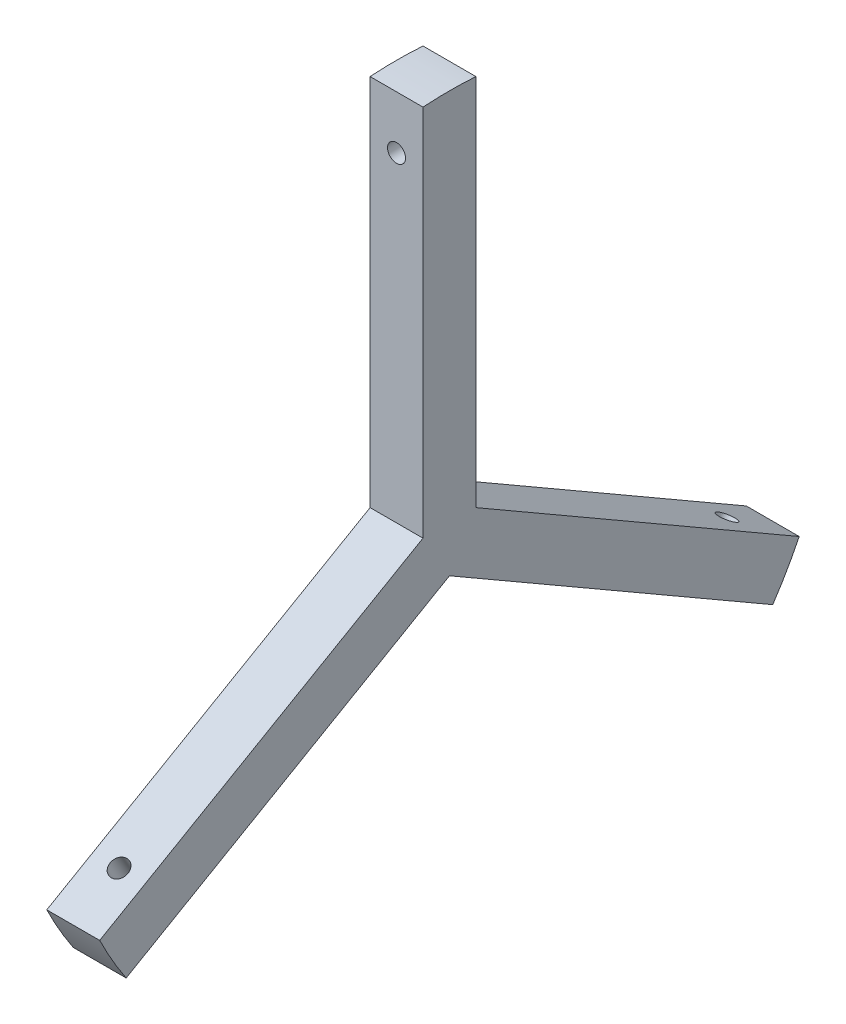
SolidWorks part; units mm, degrees
ref_plane "Plan de face" through (0, 0, 0) normal (0, 0, 1) x (1, 0, 0)
ref_plane "Plan de dessus" through (0, 0, 0) normal (0, 1, 0) x (1, 0, 0)
ref_plane "Plan de droite" through (0, 0, 0) normal (1, 0, 0) x (0, 0, -1)
sketch "Esquisse2" plane through (0, 0, 0) normal (0, 0, 1) x (1, 0, 0)
  line L0 (-5, 0) -> (5, 0)
  line L1 (5, 0) -> (5, 73.61)
  line L2 (5, 73.61) -> (-5, 73.61)
  line L3 (-5, 73.61) -> (-5, 0)
  dimension "D1" = 73.61
  dimension "D2" = 10
extrude "Boss.-Extru.1" add sketch "Esquisse2" along normal blind 5 and the other way blind 5
sketch "Esquisse3" plane through (5, 0, 0) normal (1, 0, 0) x (0, 0, -1)
  line L0 (0, 0) -> (0, 73.61) construction
  line L1 (-25.3992, 69.0892) -> (-25.3992, 83.5877)
  line L2 (-25.3992, 83.5877) -> (25.3992, 83.5877)
  line L3 (25.3992, 83.5877) -> (25.3992, 69.0892)
  line L4 (5, 75) -> (-5, 75) construction
  line L5 (-5, 0) -> (-5, 73.61) construction
  arc A0 (-25.3992, 69.0892) -> (25.3992, 69.0892) centre (0, 0) cw
  dimension "D1" = 73.61
  dimension "D2" = 30.3992
  dimension "D3" = 8.5877
extrude "Enlèv. mat.-Extru.1" cut sketch "Esquisse3" against normal through all
sketch "Esquisse5" plane through (0, 0, 0) normal (0, 1, 0) x (1, 0, 0)
  line L0 (0, 0) -> (7.3012, 0) construction
ref_plane "Plan3" through (0, 0, 0) normal (0, 0, -1) x (-1, 0, 0)
ref_plane "Plan4" through (0, 73.44, 0) normal (0, -1, 0) x (-1, 0, 0)
hole_wizard "Dégagement M31" positions "Esquisse6" profile "Esquisse7" hole size "M3" standard "ISO" end condition through all
sketch "Esquisse6" plane through (0, 0, -5) normal (0, 0, -1) x (-1, 0, 0)
  line L0 (-5.5, 73.44) -> (5.5, 73.44) construction
  line L1 (0, 63.44) -> (5, 73.44) construction
  line L3 (0, 63.44) -> (-5, 73.44) construction
  point P35 (0, 63.44)
  point P50 (0, 0)
  dimension "D1" = 10
sketch "Esquisse7" plane through (0, 63.44, -5) normal (1, 0, 0) x (0, 1, 0)
  line L0 (0, 0) -> (0, 73.6009)
  line L1 (0, 73.6009) -> (1.7, 73.6009)
  line L2 (1.7, 73.6009) -> (1.7, 0)
  line L5 (1.7, 0) -> (0, 0)
  line L11 (0, -6.35) -> (0, 107.95) construction
  dimension "Diamètre du perçage jusqu'au prochain" = 3.4
  dimension "Profondeur du perçage jusqu'au prochain" = 73.6009
pattern_circular "Répétition circulaire1" count 3 over 360 about axis through (0, 0, 0) along (1, 0, 0) of "Boss.-Extru.1", "Enlèv. mat.-Extru.1", "Dégagement M31" reverse direction yes
ref_plane "Plan1" [suppressed] through (0, 0, 0) normal (0, 0.866, 0.5) x (1, 0, 0)
ref_plane "Plan2" [suppressed] through (0, 0, 0) normal (0, 0.866, -0.5) x (1, 0, 0)
ref_plane "Plan5" [suppressed] through (0, -36.72, 63.6009) normal (0, 0.5, -0.866) x (-1, 0, 0)
ref_plane "Plan6" [suppressed] through (0, -36.72, -63.6009) normal (0, -0.5, -0.866) x (-1, 0, 0)
ref_plane "Plan7" through (0, 0, 0) normal (1, 0, 0) x (0, 0, -1)
